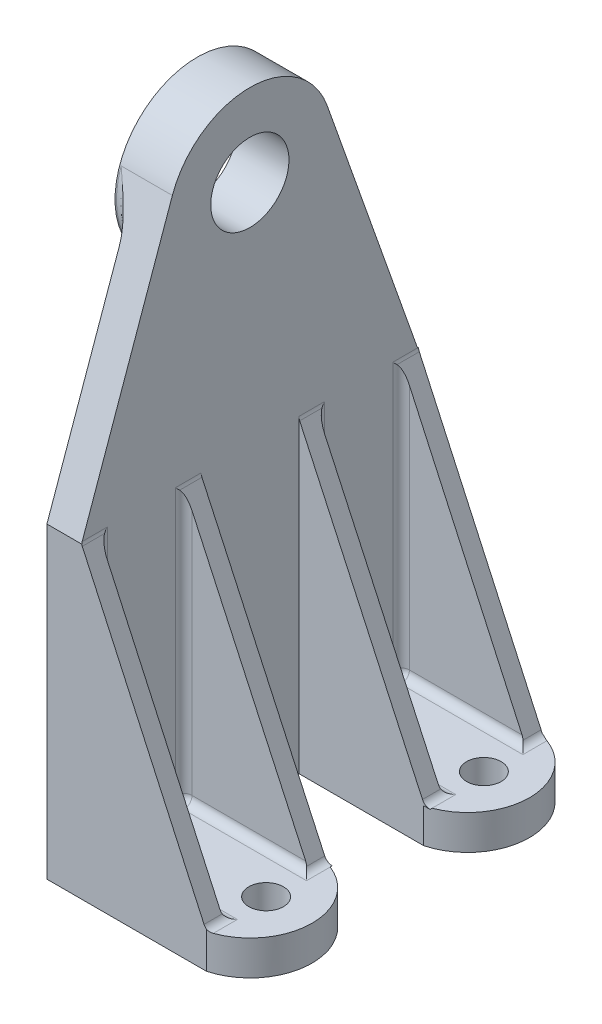
SolidWorks part; units mm, degrees
ref_plane "Front Plane" through (0, 0, 0) normal (0, 0, 1) x (1, 0, 0)
ref_plane "Top Plane" through (0, 0, 0) normal (0, 1, 0) x (1, 0, 0)
ref_plane "Right Plane" through (0, 0, 0) normal (1, 0, 0) x (0, 0, -1)
sketch "Sketch1" plane through (0, 0, 0) normal (1, 0, 0) x (0, 0, -1)
  line L0 (0, 33.2358) -> (0, 5.0201)
  line L2 (30.8829, 5.0201) -> (30.8829, 33.2358)
  line L4 (30.8829, 33.2358) -> (22.5499, 56.759)
  line L5 (0, 33.2358) -> (8.333, 56.759)
  line L6 (0, 5.0201) -> (30.8829, 5.0201)
  arc A0 (22.5499, 56.759) -> (8.333, 56.759) centre (15.4414, 54.2409) ccw
extrude "Extrude1" add sketch "Sketch1" against normal blind 3.175
ref_plane "Plane1" through (0, 5.0201, 0) normal (0, -1, 0) x (1, 0, 0)
sketch "Sketch2" plane through (0, 5.0201, 0) normal (0, -1, 0) x (1, 0, 0)
  line L0 (-3.175, 0) -> (-3.175, -30.8829) construction
  line L1 (-3.175, 0) -> (11.4455, 0)
  line L2 (-3.175, 0) -> (-3.175, -10.9741)
  line L3 (-3.175, -30.8904) -> (11.5396, -30.8904)
  line L5 (15.6616, -15.4582) -> (-3.175, -15.4582) construction
  line L6 (11.4455, -19.9423) -> (-3.175, -19.9423)
  line L7 (11.4455, -10.9741) -> (-3.175, -10.9741)
  line L9 (-3.175, -19.9423) -> (-3.175, -30.8904)
  arc A0 (11.4455, 0) -> (11.4455, -10.9741) centre (9.983, -5.487) cw
  arc A1 (11.4455, -30.9163) -> (11.4455, -19.9423) centre (9.983, -25.4293) ccw
  circle A2 centre (11.4455, -5.487) radius 1.5875
  circle A3 centre (11.4925, -25.4163) radius 1.5875
  dimension "D2" = 3.175
  dimension "D3" = 3.175
ref_plane "Plane3" through (-3.175, 0, 0) normal (1, 0, 0) x (0, 0, -1)
sketch "Sketch4" plane through (-3.175, 0, 0) normal (1, 0, 0) x (0, 0, -1)
  circle A0 centre (15.4414, 54.2409) radius 7.5413
extrude "Extrude4" add sketch "Sketch4" against normal blind 1.651
fillet "Fillet2" radius 1.524 1 edges
ref_plane "Plane4" through (-4.699, 0, 0) normal (1, 0, 0) x (0, 0, -1)
sketch "Sketch5" plane through (-4.699, 0, 0) normal (1, 0, 0) x (0, 0, -1)
  circle A0 centre (15.4414, 54.2409) radius 3.5894
extrude "Extrude5" cut sketch "Sketch5" along normal mid plane 16.383
extrude "Extrude7" add sketch "Sketch2" against normal blind 3.175 contours L3 A1 L6 L9 A3 | A0 L1 L2 L7 A2
sketch "Sketch7" plane through (0, 0, 0) normal (0, 0, 1) x (1, 0, 0)
  line L0 (11.4455, 8.1951) -> (0, 33.2358)
  line L1 (0, 33.2358) -> (0, 8.1951)
  line L2 (0, 8.1951) -> (11.4455, 8.1951)
extrude "Extrude8" add sketch "Sketch7" against normal blind 1.6002
ref_plane "Plane5" through (0, 0, -10.9741) normal (0, 0, -1) x (-1, 0, 0)
sketch "Sketch8" plane through (0, 0, -10.9741) normal (0, 0, -1) x (-1, 0, 0)
  line L0 (-11.5396, 8.1951) -> (0, 8.1951)
  line L1 (3.175, 8.1951) -> (-11.5396, 8.1951) construction
  line L2 (0, 8.1951) -> (0, 33.2358)
  line L3 (0, 33.2358) -> (-11.5396, 8.1951)
extrude "Extrude9" add sketch "Sketch8" against normal blind 1.6002
ref_plane "Plane6" through (0, 0, -15.4582) normal (0, 0, 1) x (1, 0, 0)
mirror "Mirror1" about plane through (0, 0, -15.4582) normal (0, 0, 1) of "Extrude8", "Extrude9"
fillet "Fillet4" radius 0.762 18 edges at (0, 20.7155, -9.3739) (0, 20.7155, -1.6002) (0, 8.1951, -5.487) (5.7227, 8.1951, -1.6002) (5.7698, 8.1951, -9.3739) (0, 20.7155, -29.3161) (5.7227, 8.1951, -29.3161) (0, 8.1951, -25.4293) (0, 20.7155, -21.5425) (5.7698, 8.1951, -21.5425) (11.4455, 8.1951, -30.1032) (11.5396, 8.1951, -20.7553) (11.5396, 8.1951, -10.161) (11.4455, 8.1951, -0.8001) (0, 33.2358, -30.0995) (0, 33.2358, -20.7424) (0, 33.2358, -10.174) (0, 33.2358, -0.8001)
